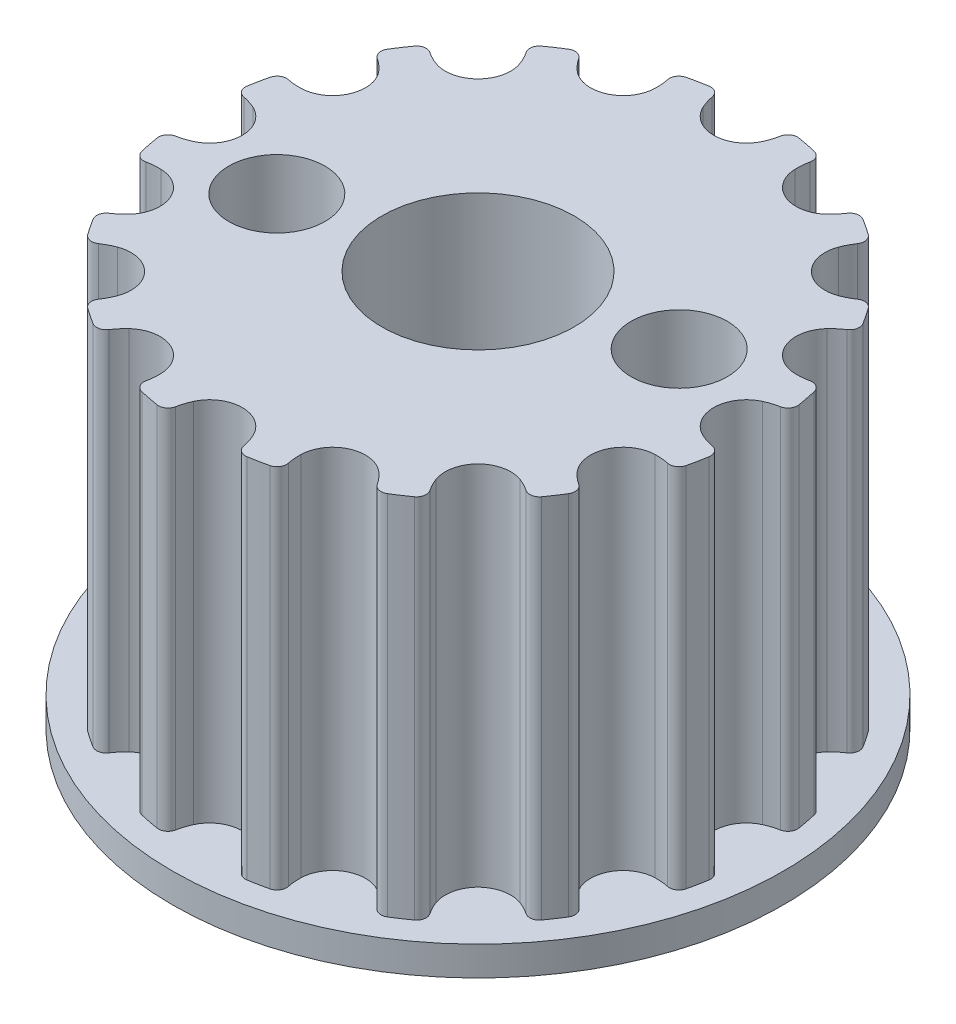
SolidWorks part; units mm, degrees
material "Alum Plate"
ref_plane "Front Plane" through (0, 0, 0) normal (0, 0, 1) x (1, 0, 0)
ref_plane "Top Plane" through (0, 0, 0) normal (0, 1, 0) x (1, 0, 0)
ref_plane "Right Plane" through (0, 0, 0) normal (1, 0, 0) x (0, 0, -1)
other "Bounding Box"
ref_plane "Default Plane" through (-8.9266, -12.7485, 0) normal (-0.1736, 0.9848, 0) x (0.9848, 0.1736, 0)
sketch "Sketch1" plane through (0, 0, 0) normal (0, 1, 0) x (1, 0, 0)
  line L0 (0, -7.8245) -> (0, 0) construction
  circle A0 centre (0, 0) radius 2.5
  arc B0 (-1.8508, -6.777) -> (-1.6633, -7.0715) centre (-1.6061, -6.8282) ccw
  arc B1 (-1.6633, -7.0715) -> (-1.1695, -7.1697) centre (0, 0) ccw
  arc B2 (-1.1695, -7.1697) -> (-0.8836, -6.9694) centre (-1.1292, -6.923) ccw
  arc B3 (-0.7739, -6.6229) -> (-0.8836, -6.9694) centre (0.61, -7.2516) ccw
  arc B4 (0.7739, -6.6229) -> (-0.7739, -6.6229) centre (0, -6.9745) ccw
  arc B5 (0.8836, -6.9694) -> (0.7739, -6.6229) centre (-0.61, -7.2516) ccw
  arc B6 (0.8836, -6.9694) -> (1.1695, -7.1697) centre (1.1292, -6.923) ccw
  arc B7 (1.1695, -7.1697) -> (1.6633, -7.0715) centre (0, 0) ccw
  arc B8 (1.6633, -7.0715) -> (1.8508, -6.777) centre (1.6061, -6.8282) ccw
  arc B9 (1.8195, -6.4149) -> (1.8508, -6.777) centre (3.3386, -6.4662) ccw
  arc B10 (3.2495, -5.8226) -> (1.8195, -6.4149) centre (2.669, -6.4436) ccw
  arc B11 (3.4834, -6.1008) -> (3.2495, -5.8226) centre (2.2115, -6.9331) ccw
  arc B12 (3.4834, -6.1008) -> (3.8242, -6.1764) centre (3.6926, -5.9639) ccw
  arc B13 (3.8242, -6.1764) -> (4.2428, -5.8967) centre (0, 0) ccw
  arc B14 (4.2428, -5.8967) -> (4.3033, -5.5529) centre (4.0968, -5.6938) ccw
  arc B15 (4.1359, -5.2303) -> (4.3033, -5.5529) centre (5.559, -4.6963) ccw
  arc B16 (5.2303, -4.1359) -> (4.1359, -5.2303) centre (4.9317, -4.9317) ccw
  arc B17 (5.5529, -4.3033) -> (5.2303, -4.1359) centre (4.6963, -5.559) ccw
  arc B18 (5.5529, -4.3033) -> (5.8967, -4.2428) centre (5.6938, -4.0968) ccw
  arc B19 (5.8967, -4.2428) -> (6.1764, -3.8242) centre (0, 0) ccw
  arc B20 (6.1764, -3.8242) -> (6.1008, -3.4834) centre (5.9639, -3.6926) ccw
  arc B21 (5.8226, -3.2495) -> (6.1008, -3.4834) centre (6.9331, -2.2115) ccw
  arc B22 (6.4149, -1.8195) -> (5.8226, -3.2495) centre (6.4436, -2.669) ccw
  arc B23 (6.777, -1.8508) -> (6.4149, -1.8195) centre (6.4662, -3.3386) ccw
  arc B24 (6.777, -1.8508) -> (7.0715, -1.6633) centre (6.8282, -1.6061) ccw
  arc B25 (7.0715, -1.6633) -> (7.1697, -1.1695) centre (0, 0) ccw
  arc B26 (7.1697, -1.1695) -> (6.9694, -0.8836) centre (6.923, -1.1292) ccw
  arc B27 (6.6229, -0.7739) -> (6.9694, -0.8836) centre (7.2516, 0.61) ccw
  arc B28 (6.6229, 0.7739) -> (6.6229, -0.7739) centre (6.9745, 0) ccw
  arc B29 (6.9694, 0.8836) -> (6.6229, 0.7739) centre (7.2516, -0.61) ccw
  arc B30 (6.9694, 0.8836) -> (7.1697, 1.1695) centre (6.923, 1.1292) ccw
  arc B31 (7.1697, 1.1695) -> (7.0715, 1.6633) centre (0, 0) ccw
  arc B32 (7.0715, 1.6633) -> (6.777, 1.8508) centre (6.8282, 1.6061) ccw
  arc B33 (6.4149, 1.8195) -> (6.777, 1.8508) centre (6.4662, 3.3386) ccw
  arc B34 (5.8226, 3.2495) -> (6.4149, 1.8195) centre (6.4436, 2.669) ccw
  arc B35 (6.1008, 3.4834) -> (5.8226, 3.2495) centre (6.9331, 2.2115) ccw
  arc B36 (6.1008, 3.4834) -> (6.1764, 3.8242) centre (5.9639, 3.6926) ccw
  arc B37 (6.1764, 3.8242) -> (5.8967, 4.2428) centre (0, 0) ccw
  arc B38 (5.8967, 4.2428) -> (5.5529, 4.3033) centre (5.6938, 4.0968) ccw
  arc B39 (5.2303, 4.1359) -> (5.5529, 4.3033) centre (4.6963, 5.559) ccw
  arc B40 (4.1359, 5.2303) -> (5.2303, 4.1359) centre (4.9317, 4.9317) ccw
  arc B41 (4.3033, 5.5529) -> (4.1359, 5.2303) centre (5.559, 4.6963) ccw
  arc B42 (4.3033, 5.5529) -> (4.2428, 5.8967) centre (4.0968, 5.6938) ccw
  arc B43 (4.2428, 5.8967) -> (3.8242, 6.1764) centre (0, 0) ccw
  arc B44 (3.8242, 6.1764) -> (3.4834, 6.1008) centre (3.6926, 5.9639) ccw
  arc B45 (3.2495, 5.8226) -> (3.4834, 6.1008) centre (2.2115, 6.9331) ccw
  arc B46 (1.8195, 6.4149) -> (3.2495, 5.8226) centre (2.669, 6.4436) ccw
  arc B47 (1.8508, 6.777) -> (1.8195, 6.4149) centre (3.3386, 6.4662) ccw
  arc B48 (1.8508, 6.777) -> (1.6633, 7.0715) centre (1.6061, 6.8282) ccw
  arc B49 (1.6633, 7.0715) -> (1.1695, 7.1697) centre (0, 0) ccw
  arc B50 (1.1695, 7.1697) -> (0.8836, 6.9694) centre (1.1292, 6.923) ccw
  arc B51 (0.7739, 6.6229) -> (0.8836, 6.9694) centre (-0.61, 7.2516) ccw
  arc B52 (-0.7739, 6.6229) -> (0.7739, 6.6229) centre (0, 6.9745) ccw
  arc B53 (-0.8836, 6.9694) -> (-0.7739, 6.6229) centre (0.61, 7.2516) ccw
  arc B54 (-0.8836, 6.9694) -> (-1.1695, 7.1697) centre (-1.1292, 6.923) ccw
  arc B55 (-1.1695, 7.1697) -> (-1.6633, 7.0715) centre (0, 0) ccw
  arc B56 (-1.6633, 7.0715) -> (-1.8508, 6.777) centre (-1.6061, 6.8282) ccw
  arc B57 (-1.8195, 6.4149) -> (-1.8508, 6.777) centre (-3.3386, 6.4662) ccw
  arc B58 (-3.2495, 5.8226) -> (-1.8195, 6.4149) centre (-2.669, 6.4436) ccw
  arc B59 (-3.4834, 6.1008) -> (-3.2495, 5.8226) centre (-2.2115, 6.9331) ccw
  arc B60 (-3.4834, 6.1008) -> (-3.8242, 6.1764) centre (-3.6926, 5.9639) ccw
  arc B61 (-3.8242, 6.1764) -> (-4.2428, 5.8967) centre (0, 0) ccw
  arc B62 (-4.2428, 5.8967) -> (-4.3033, 5.5529) centre (-4.0968, 5.6938) ccw
  arc B63 (-4.1359, 5.2303) -> (-4.3033, 5.5529) centre (-5.559, 4.6963) ccw
  arc B64 (-5.2303, 4.1359) -> (-4.1359, 5.2303) centre (-4.9317, 4.9317) ccw
  arc B65 (-5.5529, 4.3033) -> (-5.2303, 4.1359) centre (-4.6963, 5.559) ccw
  arc B66 (-5.5529, 4.3033) -> (-5.8967, 4.2428) centre (-5.6938, 4.0968) ccw
  arc B67 (-5.8967, 4.2428) -> (-6.1764, 3.8242) centre (0, 0) ccw
  arc B68 (-6.1764, 3.8242) -> (-6.1008, 3.4834) centre (-5.9639, 3.6926) ccw
  arc B69 (-5.8226, 3.2495) -> (-6.1008, 3.4834) centre (-6.9331, 2.2115) ccw
  arc B70 (-6.4149, 1.8195) -> (-5.8226, 3.2495) centre (-6.4436, 2.669) ccw
  arc B71 (-6.777, 1.8508) -> (-6.4149, 1.8195) centre (-6.4662, 3.3386) ccw
  arc B72 (-6.777, 1.8508) -> (-7.0715, 1.6633) centre (-6.8282, 1.6061) ccw
  arc B73 (-7.0715, 1.6633) -> (-7.1697, 1.1695) centre (0, 0) ccw
  arc B74 (-7.1697, 1.1695) -> (-6.9694, 0.8836) centre (-6.923, 1.1292) ccw
  arc B75 (-6.6229, 0.7739) -> (-6.9694, 0.8836) centre (-7.2516, -0.61) ccw
  arc B76 (-6.6229, -0.7739) -> (-6.6229, 0.7739) centre (-6.9745, 0) ccw
  arc B77 (-6.9694, -0.8836) -> (-6.6229, -0.7739) centre (-7.2516, 0.61) ccw
  arc B78 (-6.9694, -0.8836) -> (-7.1697, -1.1695) centre (-6.923, -1.1292) ccw
  arc B79 (-7.1697, -1.1695) -> (-7.0715, -1.6633) centre (0, 0) ccw
  arc B80 (-7.0715, -1.6633) -> (-6.777, -1.8508) centre (-6.8282, -1.6061) ccw
  arc B81 (-6.4149, -1.8195) -> (-6.777, -1.8508) centre (-6.4662, -3.3386) ccw
  arc B82 (-5.8226, -3.2495) -> (-6.4149, -1.8195) centre (-6.4436, -2.669) ccw
  arc B83 (-6.1008, -3.4834) -> (-5.8226, -3.2495) centre (-6.9331, -2.2115) ccw
  arc B84 (-6.1008, -3.4834) -> (-6.1764, -3.8242) centre (-5.9639, -3.6926) ccw
  arc B85 (-6.1764, -3.8242) -> (-5.8967, -4.2428) centre (0, 0) ccw
  arc B86 (-5.8967, -4.2428) -> (-5.5529, -4.3033) centre (-5.6938, -4.0968) ccw
  arc B87 (-5.2303, -4.1359) -> (-5.5529, -4.3033) centre (-4.6963, -5.559) ccw
  arc B88 (-4.1359, -5.2303) -> (-5.2303, -4.1359) centre (-4.9317, -4.9317) ccw
  arc B89 (-4.3033, -5.5529) -> (-4.1359, -5.2303) centre (-5.559, -4.6963) ccw
  arc B90 (-4.3033, -5.5529) -> (-4.2428, -5.8967) centre (-4.0968, -5.6938) ccw
  arc B91 (-4.2428, -5.8967) -> (-3.8242, -6.1764) centre (0, 0) ccw
  arc B92 (-3.8242, -6.1764) -> (-3.4834, -6.1008) centre (-3.6926, -5.9639) ccw
  arc B93 (-3.2495, -5.8226) -> (-3.4834, -6.1008) centre (-2.2115, -6.9331) ccw
  arc B94 (-1.8195, -6.4149) -> (-3.2495, -5.8226) centre (-2.669, -6.4436) ccw
  arc B95 (-1.8508, -6.777) -> (-1.8195, -6.4149) centre (-3.3386, -6.4662) ccw
  dimension "D1" = 5
sketch_block_instance "Block-GT2 16 Tooth Profile-1"
sketch_block "Block-GT2 16 Tooth Profile"
extrude "Boss-Extrude1" add sketch "Sketch1" along normal mid plane 9.525
sketch "Sketch2" plane through (0, -4.7625, 0) normal (0, -1, 0) x (1, 0, 0)
  circle A0 centre (0, 0) radius 7.9375
  circle A1 centre (0, 0) radius 2.5 construction
  circle A2 centre (0, 0) radius 2.5
  dimension "D1" = 15.875
extrude "Boss-Extrude2" add sketch "Sketch2" along normal blind 0.762 separate body
sketch "Sketch4" plane through (0, -4.7625, 0) normal (0, -1, 0) x (1, 0, 0)
  line L0 (-4.3596, 0.8672) -> (0, 0) construction
  line L1 (0, 0) -> (4.3596, -0.8672) construction
  line L2 (-7.1249, 1.4172) -> (-4.3596, 0.8672) construction
  circle A0 centre (-4.3596, 0.8672) radius 1.25
  circle A1 centre (4.3596, -0.8672) radius 1.25
  arc A2 (-7.0715, 1.6633) -> (-7.1697, 1.1695) centre (0, 0) ccw construction
  dimension "D1" = 2.5
  dimension "D2" = 4.445
extrude "Cut-Extrude2" cut sketch "Sketch4" against normal through all
sketch "Sketch5" plane through (0, -4.7625, 0) normal (0, 1, 0) x (1, 0, 0)
  circle A0 centre (-4.3596, -0.8672) radius 1.5
  circle A1 centre (4.3596, 0.8672) radius 1.5
  dimension "D1" = 3
extrude "Cut-Extrude3" cut sketch "Sketch5" against normal through all
